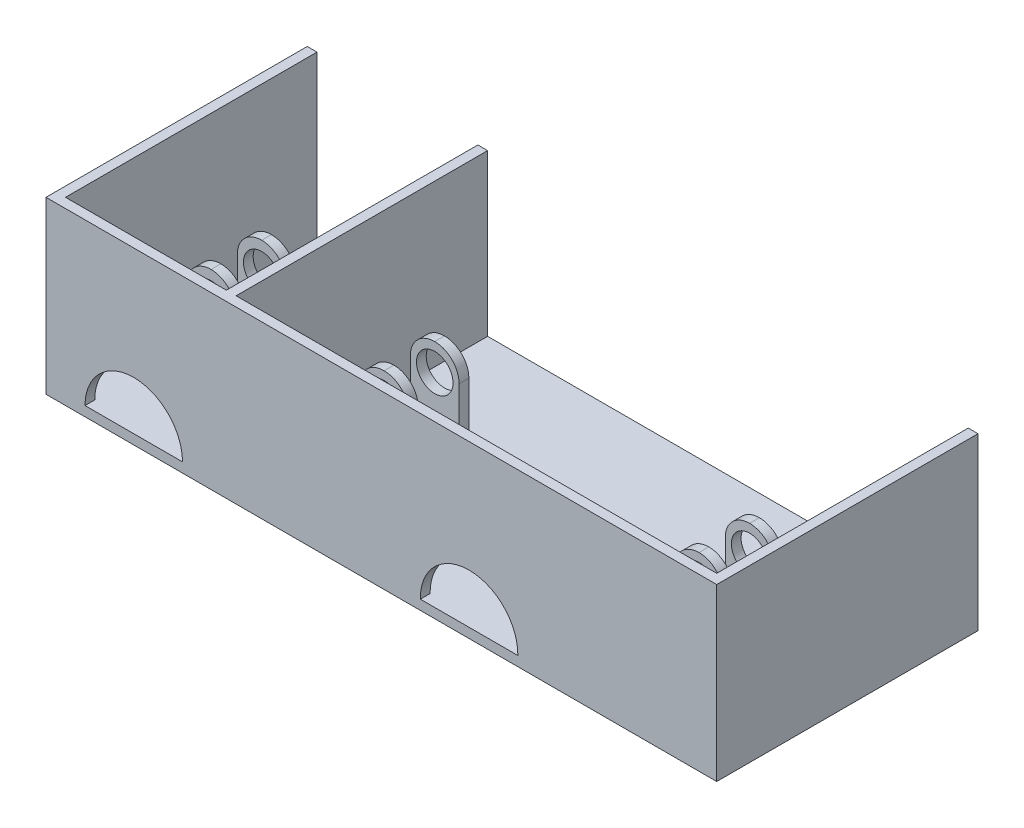
SolidWorks part; units mm, degrees
ref_plane "Plan de face" through (0, 0, 0) normal (0, 0, 1) x (1, 0, 0)
ref_plane "Plan de dessus" through (0, 0, 0) normal (0, 1, 0) x (1, 0, 0)
ref_plane "Plan de droite" through (0, 0, 0) normal (1, 0, 0) x (0, 0, -1)
sketch "Esquisse1" plane through (0, 0, 0) normal (0, 0, 1) x (1, 0, 0)
  line L1 (-17.4678, 19.1867) -> (85.1322, 19.1867)
  line L2 (-17.4678, 19.1867) -> (-17.4678, -15.8133)
  line L3 (-17.4678, -15.8133) -> (85.1322, -15.8133)
  line L4 (85.1322, 19.1867) -> (85.1322, -15.8133)
  dimension "D1" = 35
  dimension "D2" = 102.6
extrude "Boss.-Extru.1" add sketch "Esquisse1" along normal blind 53.6 and the other way blind 0.0001
sketch "Esquisse4" plane through (0, 19.1867, 0) normal (0, 1, 0) x (1, 0, 0)
  line L1 (-15.4678, -51.5999) -> (83.1322, -51.5999)
  line L2 (-15.4678, -51.5999) -> (-15.4678, 0.0001)
  line L3 (-15.4678, 0.0001) -> (83.1322, 0.0001)
  line L4 (83.1322, -51.5999) -> (83.1322, 0.0001)
  line L5 (-17.4678, -53.6) -> (-17.4678, 0.0001) construction
  line L6 (85.1322, -53.6) -> (85.1322, 0.0001) construction
  line L7 (85.1322, 0.0001) -> (-17.4678, 0.0001) construction
  dimension "D1" = 51.6
  dimension "D2" = 98.6
  dimension "D3" = 0
  dimension "D4" = 2
  dimension "D5" = 2
extrude "Enlèv. mat.-Extru.2" cut sketch "Esquisse4" against normal blind 33
sketch "Esquisse9" plane through (0, -13.8133, 0) normal (0, 1, 0) x (1, 0, 0)
  line L0 (83.1322, 0.0001) -> (-15.4678, 0.0001) construction
  line L1 (-3.4678, -25.8499) -> (6.5322, -25.8499)
  line L2 (-3.4678, -25.8499) -> (-3.4678, -27.8499)
  line L3 (-3.4678, -27.8499) -> (6.5322, -27.8499)
  line L4 (6.5322, -25.8499) -> (6.5322, -27.8499)
  line L5 (-15.4678, 0.0001) -> (-15.4678, -51.5999) construction
  line L6 (-3.4678, -36.2299) -> (6.5322, -36.2299)
  line L7 (-3.4678, -36.2299) -> (-3.4678, -38.2299)
  line L8 (-3.4678, -38.2299) -> (6.5322, -38.2299)
  line L9 (6.5322, -36.2299) -> (6.5322, -38.2299)
  line L10 (-15.4678, -51.5999) -> (83.1322, -51.5999) construction
  line L11 (61.1322, -25.8499) -> (71.1322, -25.8499)
  line L12 (61.1322, -25.8499) -> (61.1322, -27.8499)
  line L13 (61.1322, -27.8499) -> (71.1322, -27.8499)
  line L14 (71.1322, -25.8499) -> (71.1322, -27.8499)
  line L15 (61.1322, -36.2299) -> (71.1322, -36.2299)
  line L16 (61.1322, -36.2299) -> (61.1322, -38.2299)
  line L17 (61.1322, -38.2299) -> (71.1322, -38.2299)
  line L18 (71.1322, -36.2299) -> (71.1322, -38.2299)
  line L19 (83.1322, -51.5999) -> (83.1322, 0.0001) construction
  point P24 (71.1322, -37.2299)
  dimension "D1" = 25.85
  dimension "D2" = 10
  dimension "D3" = 12
  dimension "D4" = 2
  dimension "D5" = 0
  dimension "D6" = 10
  dimension "D7" = 12.38
  dimension "D8" = 2
  dimension "D9" = 13.37
  dimension "D10" = 25.85
  dimension "D11" = 2
  dimension "D12" = 2
  dimension "D13" = 10
  dimension "D14" = 10
  dimension "D15" = 12.38
  dimension "D16" = 12
  dimension "D17" = 0
extrude "Boss.-Extru.3" add sketch "Esquisse9" along normal blind 21.5
fillet "Congé2" radius 5 8 edges at (71.1322, 7.6867, 37.2299) (61.1322, 7.6867, 37.2299) (71.1322, 7.6867, 26.8499) (61.1322, 7.6867, 26.8499) (-3.4678, 7.6867, 37.2299) (6.5322, 7.6867, 37.2299) (-3.4678, 7.6867, 26.8499) (6.5322, 7.6867, 26.8499)
sketch "Esquisse10" plane through (0, 0, 25.8499) normal (0, 0, -1) x (-1, 0, 0)
  line L0 (-71.1322, -13.8133) -> (-61.1322, -13.8133) construction
  line L2 (-83.1322, -13.8133) -> (15.4678, -13.8133) construction
  line L4 (-71.1322, 2.6867) -> (-71.1322, -13.8133) construction
  line L6 (3.4678, 2.6867) -> (3.4678, -13.8133) construction
  line L7 (-83.1322, -13.8133) -> (-83.1322, 19.1867) construction
  line L8 (15.4678, -13.8133) -> (15.4678, 19.1867) construction
  circle A0 centre (-66.1322, 2.1867) radius 3.75
  circle A1 centre (-1.5322, 2.1867) radius 3.75
  point P4 (-66.1322, -13.8133)
  dimension "D1" = 7.5
  dimension "D4" = 7.5
  dimension "D2" = 16
  dimension "D3" = 5
  dimension "D5" = 16
  dimension "D6" = 5
  dimension "D7" = 64.6
  dimension "D8" = 17
  dimension "D9" = 17
extrude "Enlèv. mat.-Extru.4" cut sketch "Esquisse10" against normal blind 15
sketch "Esquisse16" plane through (-17.4678, 0, 0) normal (-1, 0, 0) x (0, 0, 1)
  line L0 (53.6, 19.1867) -> (53.6, -15.8133) construction
  line L1 (-0.0001, -15.8133) -> (53.6, -15.8133)
  line L2 (-0.0001, -15.8133) -> (-0.0001, 19.1867)
  line L3 (-0.0001, 19.1867) -> (53.6, 19.1867)
  line L4 (53.6, -15.8133) -> (53.6, 19.1867)
  dimension "D1" = 35
  dimension "D2" = 53.6001
extrude "Boss.-Extru.5" add sketch "Esquisse16" along normal blind 35
sketch "Esquisse18" plane through (0, 0, 53.6) normal (0, 0, 1) x (1, 0, 0)
  line L0 (85.1322, -15.8133) -> (85.1322, 19.1867) construction
  line L1 (-52.4678, -15.8133) -> (85.1322, -15.8133) construction
  line L2 (24.3335, -13.8133) -> (44.3308, -13.8133)
  arc A1 (44.3308, -13.8133) -> (24.3335, -13.8133) centre (34.3322, -13.6433) ccw
  point P7 (0, 0)
  point P8 (0, 0)
  point P11 (0, 0)
  dimension "D3" = 50.8
  dimension "D4" = 2
extrude "Enlèv. mat.-Extru.5" cut sketch "Esquisse18" against normal blind 2.1
sketch "Esquisse19" plane through (0, 19.1867, 0) normal (0, 1, 0) x (1, 0, 0)
  line L0 (-15.4678, 0.0001) -> (-52.4678, 0.0001) construction
  line L1 (-17.4678, -51.6) -> (-50.4678, -51.6)
  line L2 (-17.4678, -51.6) -> (-17.4678, 0.0001)
  line L3 (-17.4678, 0.0001) -> (-50.4678, 0.0001)
  line L4 (-50.4678, -51.6) -> (-50.4678, 0.0001)
  line L5 (85.1322, -53.6) -> (-52.4678, -53.6) construction
  line L6 (-52.4678, -53.6) -> (-52.4678, 0.0001) construction
  line L7 (-15.4678, 0.0001) -> (-15.4678, -51.5999) construction
  dimension "D1" = 2
  dimension "D2" = 2
  dimension "D3" = 2
extrude "Enlèv. mat.-Extru.6" cut sketch "Esquisse19" against normal blind 33
sketch "Esquisse20" plane through (0, 0, 53.6) normal (0, 0, 1) x (1, 0, 0)
  line L0 (-52.4678, -15.8133) -> (-52.4678, 19.1867) construction
  line L1 (-24.4678, -13.8133) -> (-44.4678, -13.8133)
  line L2 (-52.4678, -15.8133) -> (85.1322, -15.8133) construction
  arc A1 (-44.4678, -13.8133) -> (-24.4678, -13.8133) centre (-34.4678, -13.8133) cw
  point P5 (0, 0)
  point P9 (0, 0)
  dimension "D1" = 18
  dimension "D2" = 20
  dimension "D3" = 2
extrude "Enlèv. mat.-Extru.7" cut sketch "Esquisse20" against normal blind 2.5
sketch "Esquisse21" plane through (0, -13.8133, 0) normal (0, 1, 0) x (1, 0, 0)
  line L0 (-50.4678, 0.0001) -> (-50.4678, -51.6) construction
  line L1 (-28.9678, -27.8499) -> (-38.9678, -27.8499)
  line L2 (-28.9678, -27.8499) -> (-28.9678, -25.8499)
  line L3 (-28.9678, -25.8499) -> (-38.9678, -25.8499)
  line L4 (-38.9678, -27.8499) -> (-38.9678, -25.8499)
  line L6 (-17.4678, 0.0001) -> (-50.4678, 0.0001) construction
  line L8 (-17.4678, -51.6) -> (-17.4678, 0.0001) construction
  line L9 (-50.4678, 0.0001) -> (-50.4678, -51.6) construction
  line L10 (-28.9678, -38.2299) -> (-38.9678, -38.2299)
  line L11 (-28.9678, -38.2299) -> (-28.9678, -36.2299)
  line L12 (-28.9678, -36.2299) -> (-38.9678, -36.2299)
  line L13 (-38.9678, -38.2299) -> (-38.9678, -36.2299)
  point P8 (-38.9678, -26.8499)
  point P15 (-38.9678, -37.2299)
  dimension "D1" = 2
  dimension "D2" = 11.5
  dimension "D3" = 25.85
  dimension "D4" = 10
  dimension "D5" = 11.5
  dimension "D6" = 2
  dimension "D7" = 10
  dimension "D8" = 11.5
  dimension "D9" = 12.38
extrude "Boss.-Extru.6" add sketch "Esquisse21" along normal blind 21.75
fillet "Congé3" radius 5 4 edges at (-28.9678, 7.9367, 37.2299) (-38.9678, 7.9367, 37.2299) (-38.9678, 7.9367, 26.8499) (-28.9678, 7.9367, 26.8499)
sketch "Esquisse22" plane through (0, 0, 25.8499) normal (0, 0, -1) x (-1, 0, 0)
  line L0 (28.9678, -13.8133) -> (38.9678, -13.8133) construction
  line L1 (50.4678, -13.8133) -> (50.4678, 19.1867) construction
  circle A0 centre (33.9678, 2.1867) radius 3.75
  dimension "D1" = 7.5
  dimension "D2" = 16
  dimension "D3" = 16.5
extrude "Enlèv. mat.-Extru.8" cut sketch "Esquisse22" against normal blind 15
